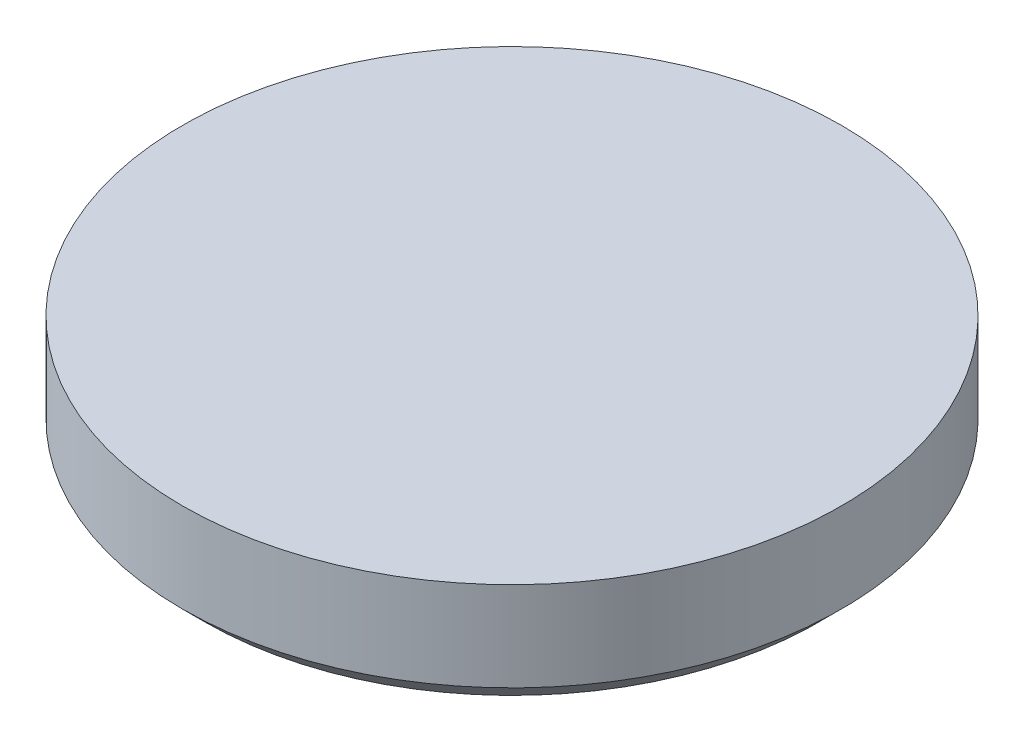
SolidWorks part; units mm, degrees
ref_plane "Front Plane" through (0, 0, 0) normal (0, 0, 1) x (1, 0, 0)
ref_plane "Top Plane" through (0, 0, 0) normal (0, 1, 0) x (1, 0, 0)
ref_plane "Right Plane" through (0, 0, 0) normal (1, 0, 0) x (0, 0, -1)
sketch "Sketch1" plane through (0, 0, 0) normal (0, 1, 0) x (1, 0, 0)
  circle A0 centre (0, 0) radius 37.465
  dimension "D1" = 74.93
extrude "Boss-Extrude1" add sketch "Sketch1" along normal blind 12.7
hole_wizard "M3 Clearance Hole1" positions "Sketch2" profile "Sketch3" hole size "M3" standard "DIN"
sketch "Sketch2" plane through (0, 0, 0) normal (0, -1, 0) x (-1, 0, 0)
  point P0 (0, 0)
sketch "Sketch3" plane through (0, 0, 0) normal (1, 0, 0) x (0, 0, -1)
  line L0 (0, 0) -> (0, 10.5465)
  line L1 (0, 10.5465) -> (1.7, 9.525)
  line L2 (1.7, 9.525) -> (1.7, 0.025)
  line L3 (1.7, 0.025) -> (1.725, 0)
  line L5 (1.725, 0) -> (0, 0)
  line L6 (-1.7, 0.025) -> (-1.725, 0) construction
  line L10 (0, 10.5465) -> (-1.7, 9.525) construction
  line L11 (0, -6.35) -> (0, 107.95) construction
  dimension "Hole Dia." = 3.4
  dimension "Hole Depth" = 9.525
  dimension "Near C'Sink Dia." = 3.45
  dimension "Near C'Sink Angle" = 90
  dimension "Drill Angle" = 118
thread "Thread1" pitch 0.5 method extrude profile "Thread Profile1" start angle 0, offset 0, length 10, pitch 0.5, diameter 3.4
ref_plane "Plane1" through (1.7, 0.025, 0) normal (0, 0, 1) x (1, 0, 0)
sketch "Thread Profile1" plane through (1.7, 0.025, 0) normal (0, 0, 1) x (1, 0, 0)
  line L0 (0, 0) -> (0, 0.5) construction
  line L11 (0, 0) -> (0, 0.4375)
  line L12 (0, 0.4375) -> (-0.2706, 0.2812)
  line L13 (-0.2706, 0.2812) -> (-0.2706, 0.1562)
  line L15 (-0.2706, 0.1562) -> (0, 0)
  line L17 (-0.2706, 0.2187) -> (0, 0.2187) construction
  point P2 (0, 0)
  dimension "Pitch" = 0.5
  dimension "Profile_Angle" = 60
  dimension "Profile_Land" = 0.125
  dimension "Profile_Height" = 0.2706
chamfer "Chamfer1" distance 2.54 angle 45 1 edges at (0, 0, 37.465)
